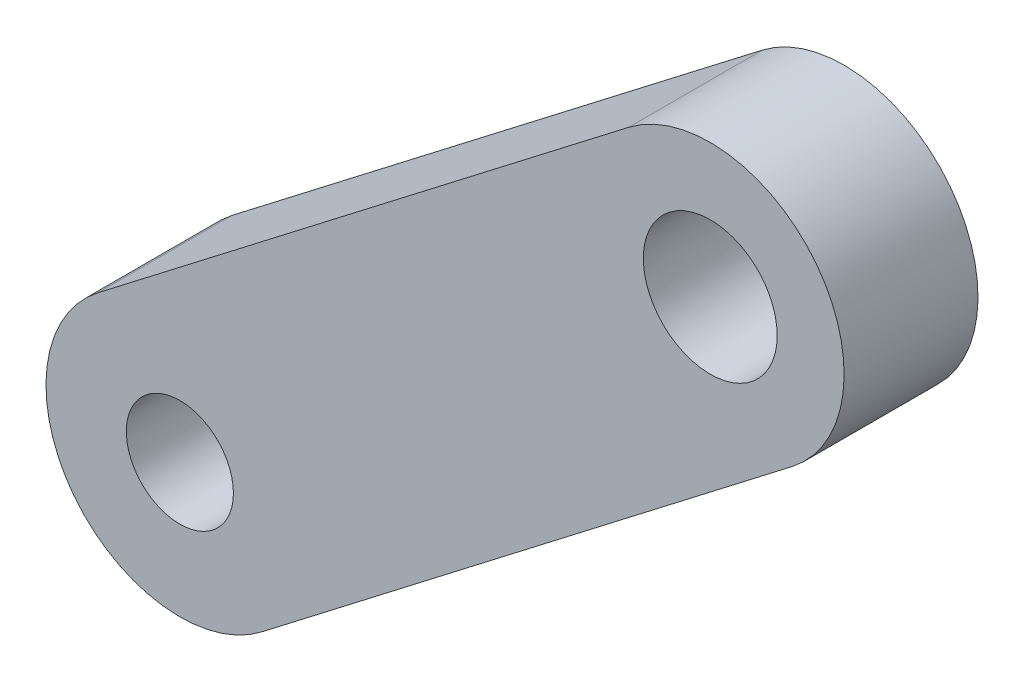
SolidWorks part; units mm, degrees
ref_plane "Front Plane" through (0, 0, 0) normal (0, 0, 1) x (1, 0, 0)
ref_plane "Top Plane" through (0, 0, 0) normal (0, 1, 0) x (1, 0, 0)
ref_plane "Right Plane" through (0, 0, 0) normal (1, 0, 0) x (0, 0, -1)
sketch "Sketch1" plane through (0, 0, 0) normal (0, 0, 1) x (0.9998, -0.022, 0)
  line L0 (-41.8829, 111.4723) -> (-17.0715, 91.626) construction
  line L1 (-1.7639, 79.3817) -> (-1.7639, 99.3817) construction
  line L2 (-1.7639, 99.3817) -> (-51.7712, 99.3817) construction
  line L3 (-46.2352, 83.6971) -> (-26.7675, 99.3817) construction
  line L4 (-46.2352, 83.6971) -> (-49.3722, 87.5906) construction
  line L5 (-49.3722, 87.5906) -> (-43.0983, 79.8035) construction
  line L6 (-49.3722, 87.5906) -> (-29.9044, 103.2753)
  line L7 (-43.0983, 79.8035) -> (-23.6306, 95.4882)
  line L8 (-29.9044, 103.2753) -> (-23.6306, 95.4882) construction
  circle A0 centre (-1.7639, 79.3817) radius 2.5 construction
  circle A1 centre (-1.7639, 79.3817) radius 2.5 construction
  circle A3 centre (-26.7675, 99.3817) radius 2.5
  arc A4 (-22.8629, 96.2585) -> (-30.6611, 96.2448) centre (-26.7675, 99.3817) ccw
  circle A5 centre (-46.2352, 83.6971) radius 2 construction
  circle A6 centre (-46.2352, 83.6971) radius 2
  arc A7 (-49.3722, 87.5906) -> (-43.0983, 79.8035) centre (-46.2352, 83.6971) ccw
  arc A8 (-23.6306, 95.4882) -> (-29.9044, 103.2753) centre (-26.7675, 99.3817) ccw
  point P18 (-26.7675, 99.3817)
  dimension "D1" = 5
  dimension "D2" = 5
  dimension "D4" = 5
  dimension "D5" = 4
  dimension "D6" = 10
  dimension "D3" = 20
  dimension "D7" = 25
extrude "Boss-Extrude1" add sketch "Sketch1" along normal blind 5 contours L7 A8 L6 A7 A3 A6 region at (-34.7121, 92.1394, 0)
sketch "Sketch2" plane through (0, 0, 0) normal (0, 0, -1) x (-1, 0, 0)
  circle A0 centre (44.3801, 84.6953) radius 2
